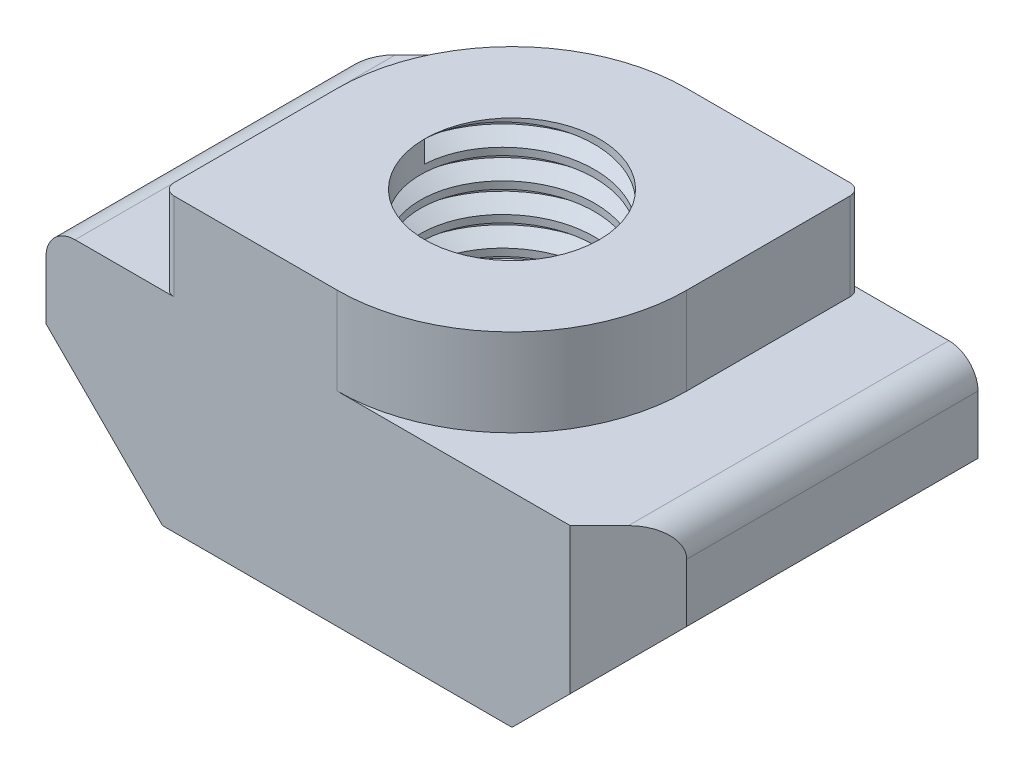
SolidWorks part; units mm, degrees
ref_plane "Front Plane" through (0, 0, 0) normal (0, 0, 1) x (1, 0, 0)
ref_plane "Top Plane" through (0, 0, 0) normal (0, 1, 0) x (1, 0, 0)
ref_plane "Right Plane" through (0, 0, 0) normal (1, 0, 0) x (0, 0, -1)
sketch "Sketch1" plane through (0, 0, 0) normal (0, 1, 0) x (1, 0, 0)
  line L0 (-5, 2) -> (-4, 3)
  line L1 (-5, -3) -> (4, -3)
  line L2 (-5, -3) -> (-5, 2)
  line L3 (-4, 3) -> (5, 3)
  line L4 (5, -2) -> (5, 3)
  line L5 (-5, -3) -> (5, 3) construction
  line L6 (-5, 3) -> (5, -3) construction
  line L7 (4, -3) -> (5, -2)
  point P0 (0, 0)
  dimension "D1" = 10
  dimension "D2" = 6
extrude "Boss-Extrude1" add sketch "Sketch1" along normal blind 3.5
sketch "Sketch2" plane through (0, 3.5, 0) normal (0, 1, 0) x (1, 0, 0)
  line L0 (-3, 0) -> (-3, -2.8)
  line L1 (-5, -3) -> (4, -3) construction
  line L2 (3, 0) -> (3, 2.8)
  line L3 (5, 3) -> (-4, 3) construction
  line L4 (0, -3) -> (-2.8, -3)
  line L5 (0, 3) -> (2.8, 3)
  circle A0 centre (0, 0) radius 3
  arc A1 (3, 2.8) -> (2.8, 3) centre (2.8, 2.8) ccw
  arc A2 (-3, -2.8) -> (-2.8, -3) centre (-2.8, -2.8) ccw
  point P15 (3, 3)
  point P18 (-3, -3)
  line M5 (5, 3) -> (-4, 3)
  line M8 (-5, -3) -> (4, -3)
  dimension "D1" = 6
  dimension "D2" = 0.2
extrude "Boss-Extrude2" add sketch "Sketch2" along normal blind 1.5 contours L0 A2 A0 M8 | A0 | L2 A1 A0 M5 region at (-2.3271, 3.5, 2.3271) region at (0, 3.5, 0) region at (2.3271, 3.5, -2.3271)
sketch "Sketch3" plane through (0, 5, 0) normal (0, 1, 0) x (1, 0, 0)
  circle A0 centre (0, 0) radius 1.5
  dimension "D1" = 3
extrude "Cut-Extrude1" cut sketch "Sketch3" against normal up to next
thread "Thread1" pitch 0.5 method cut profile "Thread Profile1" start angle 0, offset 0, length 0, pitch 0.5, diameter 3
ref_plane "Plane1" through (-1.5, 5, 0) normal (0, 0, 1) x (-1, 0, 0)
sketch "Thread Profile1" plane through (-1.5, 5, 0) normal (0, 0, 1) x (-1, 0, 0)
  line L0 (0, 0) -> (0, 0.5) construction
  line L1 (0, 0) -> (0.2706, 0.1562)
  line L2 (0.2706, 0.1562) -> (0.2706, 0.2187)
  line L3 (0.2706, 0.2187) -> (0, 0.375)
  line L4 (0.2706, 0.1875) -> (0, 0.1875) construction
  line L11 (0, 0) -> (0, 0.375)
  point P2 (0, 0)
  dimension "Pitch" = 0.5
  dimension "Profile_Angle" = 60
  dimension "Profile_Land" = 0.0625
  dimension "Profile_Height" = 0.2706
chamfer "Chamfer1" distance 2 angle 45 2 edges at (5, 0, -0.5) (-5, 0, 0.5)
fillet "Fillet1" radius 0.5 2 edges at (5, 3.5, -0.5) (-5, 3.5, 0.5)
